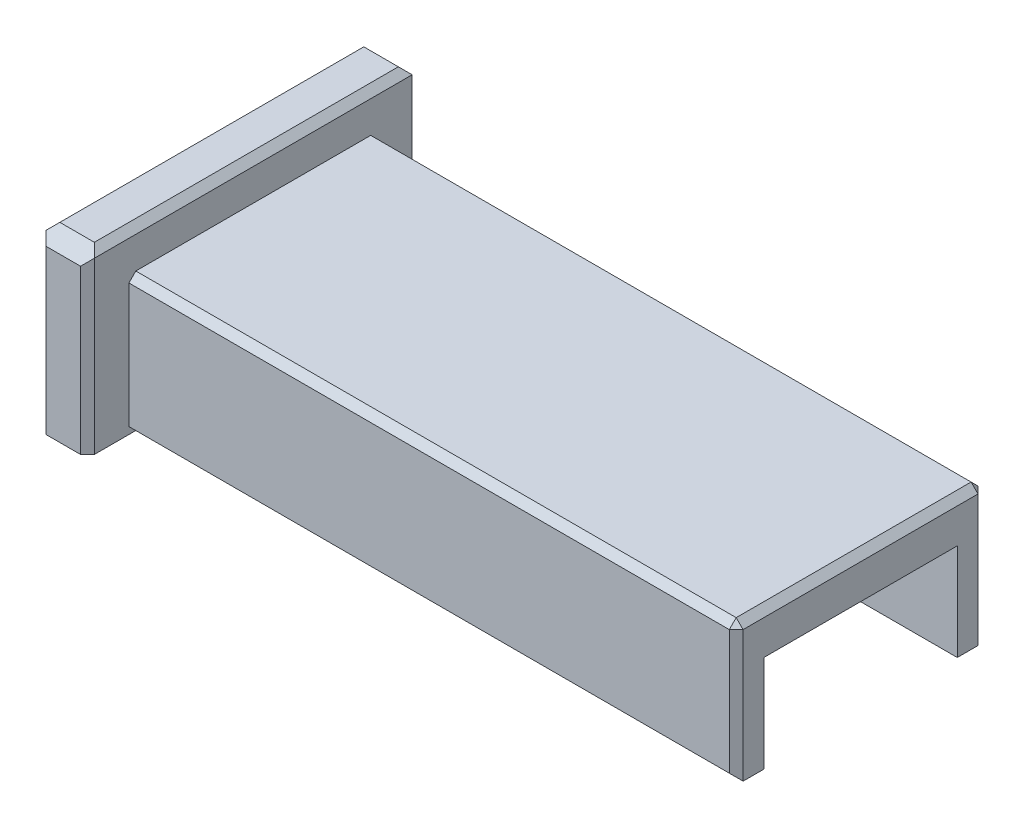
SolidWorks part; units mm, degrees
material "CA"
ref_plane "前视基准面" through (0, 0, 0) normal (0, 0, 1) x (1, 0, 0)
ref_plane "上视基准面" through (0, 0, 0) normal (0, 1, 0) x (1, 0, 0)
ref_plane "右视基准面" through (0, 0, 0) normal (1, 0, 0) x (0, 0, -1)
sketch "草图1" plane through (0, 0, 0) normal (0, 1, 0) x (1, 0, 0)
  line L1 (-23.725, -9) -> (23.725, -9)
  line L2 (-23.725, -9) -> (-23.725, 9)
  line L3 (-23.725, 9) -> (23.725, 9)
  line L4 (23.725, -9) -> (23.725, 9)
  line L5 (-23.725, -9) -> (23.725, 9) construction
  line L6 (-23.725, 9) -> (23.725, -9) construction
  point P0 (0, 0)
  dimension "D1" = 47.45
  dimension "D2" = 18
extrude "凸台-拉伸1" add sketch "草图1" along normal blind 10
sketch "草图2" plane through (-23.725, 0, 0) normal (-1, 0, 0) x (0, 0, 1)
  line L0 (12, 0) -> (12, 12.8)
  line L1 (-12, 0) -> (12, 0)
  line L2 (-12, 0) -> (-12, 12.8)
  line L3 (-12, 12.8) -> (12, 12.8)
  line L4 (0, 0) -> (0, 12.8) construction
  line L5 (-9, 0) -> (9, 0) construction
  dimension "D1" = 24
  dimension "D2" = 12.8
extrude "凸台-拉伸2" add sketch "草图2" against normal blind 3.5
sketch "草图3" plane through (-23.725, 0, 0) normal (-1, 0, 0) x (0, 0, 1)
  line L0 (-12, 0) -> (12, 0) construction
  line L1 (-7, 0) -> (7, 0)
  line L2 (-7, 0) -> (-7, 7)
  line L3 (-7, 7) -> (7, 7)
  line L4 (0, 0) -> (0, 7) construction
  line L5 (7, 0) -> (7, 7)
  dimension "D1" = 14
  dimension "D2" = 7
extrude "切除-拉伸1" cut sketch "草图3" against normal up to surface (47.45 mm away) up to face at (23.725, 5, 0)
chamfer "倒角1" distance 1 2 edges at (-21.975, 12.8, -12) (-21.975, 12.8, 12)
chamfer "倒角2" distance 0.5 angle 45 16 edges at (1.75, 0, 9) (1.75, 0, -9) (1.75, 10, -9) (1.75, 10, 9) (23.725, 5, -9) (23.725, 10, 0) (23.725, 5, 9) (-20.225, 5.9, -12) (-20.225, 12.8, 0) (-20.225, 5.9, 12) (-23.725, 12.8, 0) (-23.725, 5.9, -12) (-23.725, 5.9, 12) (-23.725, 3.5, 7) (-23.725, 7, 0) (-23.725, 3.5, -7)
